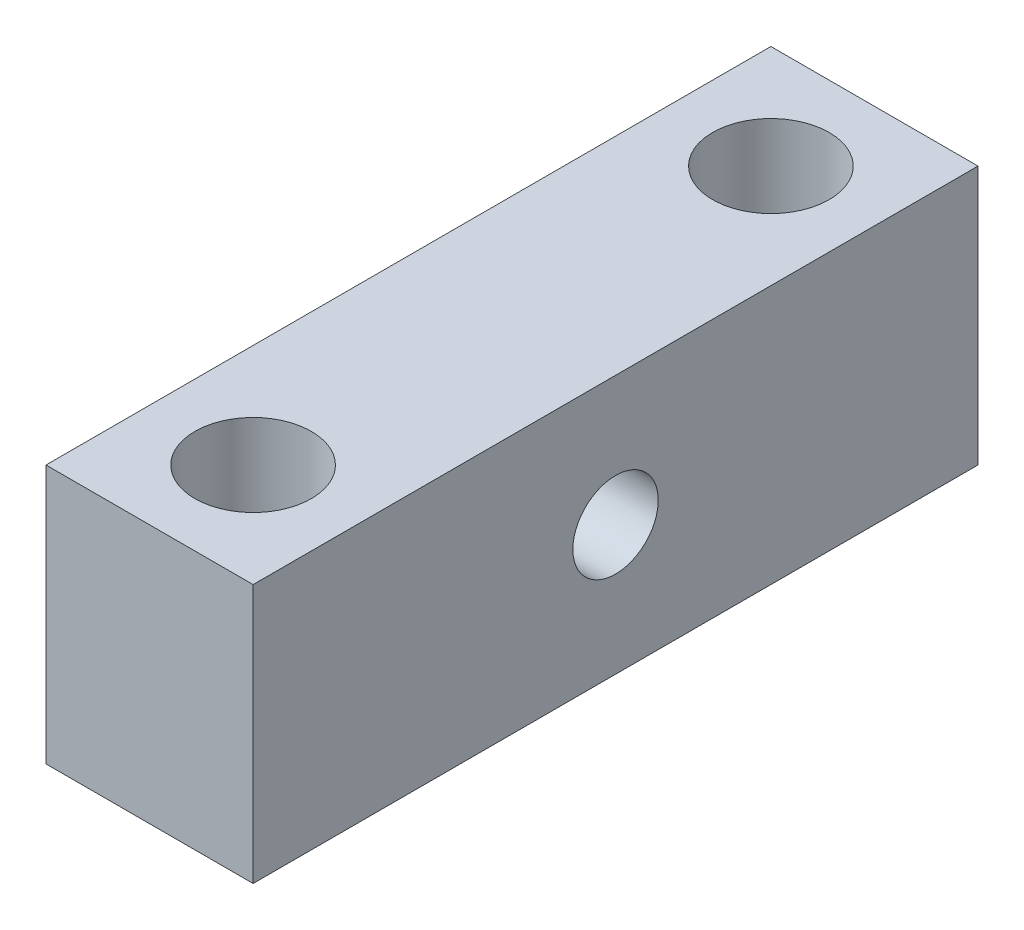
SolidWorks part; units mm, degrees
ref_plane "Front" through (0, 0, 0) normal (0, 0, 1) x (1, 0, 0)
ref_plane "Top" through (0, 0, 0) normal (0, 1, 0) x (1, 0, 0)
ref_plane "Right" through (0, 0, 0) normal (1, 0, 0) x (0, 0, -1)
sketch "Esquisse1" plane through (0, 0, 0) normal (0, 0, 1) x (1, 0, 0)
  line L1 (0, 0) -> (8, 0)
  line L2 (0, 0) -> (0, 10)
  line L3 (0, 10) -> (8, 10)
  line L4 (8, 0) -> (8, 10)
  dimension "D1" = 8
  dimension "D2" = 10
extrude "Boss.-Extru.1" add sketch "Esquisse1" along normal blind 28
sketch "Esquisse2" plane through (0, 10, 0) normal (0, 1, 0) x (1, 0, 0)
  line L0 (4, 0) -> (4, -28) construction
  line L1 (8, 0) -> (0, 0) construction
  line L2 (8, -28) -> (0, -28) construction
  line L3 (4, -14) -> (0, -14) construction
  line L4 (0, -28) -> (0, 0) construction
  circle A0 centre (4, -24) radius 2.25
  circle A1 centre (4, -4) radius 2.25
  dimension "D1" = 20
  dimension "D2" = 4.5
extrude "Enlèv. mat.-Extru.1" cut sketch "Esquisse2" against normal through all
sketch "Esquisse3" plane through (0, 0, 0) normal (-1, 0, 0) x (0, 0, 1)
  line L0 (14, 0) -> (14, 10) construction
  line L1 (28, 0) -> (0, 0) construction
  line L2 (28, 10) -> (0, 10) construction
  circle A0 centre (14, 5) radius 1.65
  dimension "D1" = 3.3
extrude "Enlèv. mat.-Extru.2" cut sketch "Esquisse3" against normal through all both and the other way through all
